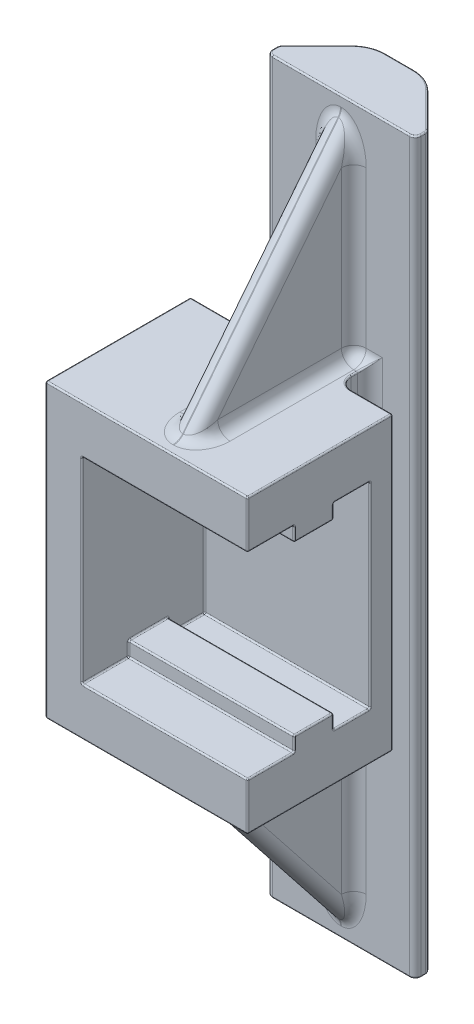
SolidWorks part; units mm, degrees
ref_plane "Front Plane" through (0, 0, 0) normal (0, 0, 1) x (1, 0, 0)
ref_plane "Top Plane" through (0, 0, 0) normal (0, 1, 0) x (1, 0, 0)
ref_plane "Right Plane" through (0, 0, 0) normal (1, 0, 0) x (0, 0, -1)
sketch "Sketch15" plane through (0, 0, 0) normal (0, 1, 0) x (1, 0, 0)
  line L0 (-3.964, 1.5536) -> (-3.964, 2.5104) construction
  line L1 (-5.6176, 4.164) -> (-9.3853, 4.164)
  line L2 (-10.187, 4.9657) -> (-10.187, 5.534)
  line L3 (-9.9522, 6.1008) -> (-5.2214, 10.8317)
  line L4 (-1.9335, 12.1936) -> (1.9335, 12.1936)
  line L5 (5.2214, 10.8317) -> (9.9522, 6.1008)
  line L6 (10.187, 5.534) -> (10.187, 4.9657)
  line L7 (9.3853, 4.164) -> (5.6176, 4.164)
  line L8 (3.964, 2.5104) -> (3.964, 1.5536) construction
  line L9 (-5.6176, 4.164) -> (5.6176, 4.164)
  line L130 (-14.3277, 0) -> (-9.4961, 0) construction
  line L131 (-7.9763, 0) -> (-5.6176, 0) construction
  line L132 (-4.064, 1.5536) -> (-4.064, 2.5104) construction
  line L133 (-5.6176, 4.064) -> (-9.3853, 4.064) construction
  line L134 (-10.287, 4.9657) -> (-10.287, 5.534) construction
  line L135 (-10.0229, 6.1716) -> (-5.2921, 10.9024) construction
  line L136 (-1.9335, 12.2936) -> (1.9335, 12.2936) construction
  line L137 (5.2921, 10.9024) -> (10.0229, 6.1716) construction
  line L138 (10.287, 5.534) -> (10.287, 4.9657) construction
  line L139 (9.3853, 4.064) -> (5.6176, 4.064) construction
  line L140 (4.064, 2.5104) -> (4.064, 1.5536) construction
  line L141 (5.6176, 0) -> (7.9763, 0) construction
  line L142 (9.4961, 0) -> (14.3277, 0) construction
  arc A0 (-5.6176, -0.1) -> (-3.964, 1.5536) centre (-5.6176, 1.5536) ccw construction
  arc A1 (-3.964, 2.5104) -> (-5.6176, 4.164) centre (-5.6176, 2.5104) ccw construction
  arc A2 (-10.187, 4.9657) -> (-9.3853, 4.164) centre (-9.3853, 4.9657) ccw
  arc A3 (-9.9522, 6.1008) -> (-10.187, 5.534) centre (-9.3853, 5.534) ccw
  arc A4 (-1.9335, 12.1936) -> (-5.2214, 10.8317) centre (-1.9335, 7.5438) ccw
  arc A5 (5.2214, 10.8317) -> (1.9335, 12.1936) centre (1.9335, 7.5438) ccw
  arc A6 (10.187, 5.534) -> (9.9522, 6.1008) centre (9.3853, 5.534) ccw
  arc A7 (9.3853, 4.164) -> (10.187, 4.9657) centre (9.3853, 4.9657) ccw
  arc A8 (5.6176, 4.164) -> (3.964, 2.5104) centre (5.6176, 2.5104) ccw construction
  arc A9 (3.964, 1.5536) -> (5.6176, -0.1) centre (5.6176, 1.5536) ccw construction
  arc A151 (-19.05, 3.2025) -> (-15.8475, 0) centre (-15.8751, 3.1749) ccw construction
  arc A152 (-14.3277, 0) -> (-15.8475, 0) centre (-15.0876, 0.0567) ccw construction
  arc A153 (-7.9763, 0) -> (-9.4961, 0) centre (-8.7362, 0.0567) ccw construction
  arc A154 (-5.6176, 0) -> (-4.064, 1.5536) centre (-5.6176, 1.5536) ccw construction
  arc A155 (-4.064, 2.5104) -> (-5.6176, 4.064) centre (-5.6176, 2.5104) ccw construction
  arc A156 (-10.287, 4.9657) -> (-9.3853, 4.064) centre (-9.3853, 4.9657) ccw construction
  arc A157 (-10.0229, 6.1716) -> (-10.287, 5.534) centre (-9.3853, 5.534) ccw construction
  arc A158 (-1.9335, 12.2936) -> (-5.2921, 10.9024) centre (-1.9335, 7.5438) ccw construction
  arc A159 (5.2921, 10.9024) -> (1.9335, 12.2936) centre (1.9335, 7.5438) ccw construction
  arc A160 (10.287, 5.534) -> (10.0229, 6.1716) centre (9.3853, 5.534) ccw construction
  arc A161 (9.3853, 4.064) -> (10.287, 4.9657) centre (9.3853, 4.9657) ccw construction
  arc A162 (5.6176, 4.064) -> (4.064, 2.5104) centre (5.6176, 2.5104) ccw construction
  arc A163 (4.064, 1.5536) -> (5.6176, 0) centre (5.6176, 1.5536) ccw construction
  arc A164 (9.4961, 0) -> (7.9763, 0) centre (8.7362, 0.0567) ccw construction
  point P0 (11.9119, 0)
  dimension "D1" = 0.1
extrude "Boss-Extrude6" add sketch "Sketch15" along normal mid plane 100
sketch "Sketch1" plane through (0, 0, 0) normal (0, 1, 0) x (1, 0, 0)
  line L5 (11.35, -0.1) -> (11.35, -20)
  line L6 (5.6176, -0.1) -> (8.093, -0.1) construction
  line L7 (-16.35, -20) -> (11.35, -20)
  line L8 (-5.6176, -0.1) -> (-3.964, -0.1)
  line L9 (-3.964, -0.1) -> (-3.964, 1.5536)
  line L10 (-3.964, 2.5104) -> (-3.964, 5)
  line L11 (3.964, 1.5536) -> (3.964, -0.1)
  line L12 (3.964, 2.5104) -> (3.964, 5)
  line L13 (3.964, -0.1) -> (5.6176, -0.1)
  line L14 (-14.3277, 0) -> (-9.4961, 0) construction
  line L15 (-14.4445, -0.1) -> (-16.35, -0.1)
  line L16 (5.6176, 0) -> (7.9763, 0) construction
  line L17 (4.064, 2.5104) -> (4.064, 1.5536) construction
  line L18 (9.3853, 4.064) -> (5.6176, 4.064) construction
  line L19 (-7.9763, 0) -> (-5.6176, 0) construction
  line L20 (-4.064, 1.5536) -> (-4.064, 2.5104) construction
  line L21 (-5.6176, 4.064) -> (-9.3853, 4.064) construction
  line L22 (-14.4445, -0.1) -> (-9.3794, -0.1)
  line L23 (-8.093, -0.1) -> (-5.6176, -0.1)
  line L24 (-3.964, 1.5536) -> (-3.964, 2.5104)
  line L26 (-16.35, -0.1) -> (-16.35, -20)
  line L27 (3.964, 2.5104) -> (3.964, 1.5536)
  line L28 (5.6176, -0.1) -> (11.35, -0.1)
  line L30 (9.3853, 4.164) -> (5.6176, 4.164) construction
  line L31 (-5.6176, 4.164) -> (-9.3853, 4.164) construction
  line L32 (3.964, 5) -> (-3.964, 5)
  line L35 (9.3794, -0.1) -> (14.4445, -0.1) construction
  line L36 (9.4961, 0) -> (14.3277, 0) construction
  arc A0 (-8.093, -0.1) -> (-9.3794, -0.1) centre (-8.7362, -0.1) ccw
  arc A10 (-19.05, 3.2025) -> (-15.8475, 0) centre (-15.8751, 3.1749) ccw construction
  arc A11 (-14.3277, 0) -> (-15.8475, 0) centre (-15.0876, 0.0567) ccw construction
  arc A12 (-7.9763, 0) -> (-9.4961, 0) centre (-8.7362, 0.0567) ccw construction
  arc A15 (9.4961, 0) -> (7.9763, 0) centre (8.7362, 0.0567) ccw construction
  arc A16 (4.064, 1.5536) -> (5.6176, 0) centre (5.6176, 1.5536) ccw construction
  arc A17 (5.6176, 4.064) -> (4.064, 2.5104) centre (5.6176, 2.5104) ccw construction
  arc A18 (-5.6176, 0) -> (-4.064, 1.5536) centre (-5.6176, 1.5536) ccw construction
  arc A19 (-4.064, 2.5104) -> (-5.6176, 4.064) centre (-5.6176, 2.5104) ccw construction
  arc A23 (-5.6176, -0.1) -> (-3.964, 1.5536) centre (-5.6176, 1.5536) ccw construction
  arc A24 (-3.964, 2.5104) -> (-5.6176, 4.164) centre (-5.6176, 2.5104) ccw construction
  arc A25 (5.6176, 4.164) -> (3.964, 2.5104) centre (5.6176, 2.5104) ccw construction
  arc A26 (3.964, 1.5536) -> (5.6176, -0.1) centre (5.6176, 1.5536) ccw construction
  arc A30 (15.7315, -0.097) -> (14.4445, -0.1) centre (15.0876, 0.0567) ccw construction
  arc A31 (15.7315, -0.097) -> (19.15, 3.2034) centre (15.8751, 3.1749) ccw construction
  arc A32 (15.8475, 0) -> (19.05, 3.2025) centre (15.8751, 3.1749) ccw construction
  arc A33 (15.8475, 0) -> (14.3277, 0) centre (15.0876, 0.0567) ccw construction
  arc A34 (-19.15, 3.2034) -> (-15.7315, -0.097) centre (-15.8751, 3.1749) ccw construction
  arc A35 (-14.4445, -0.1) -> (-15.7315, -0.097) centre (-15.0876, 0.0567) ccw construction
  arc A36 (-8.093, -0.1) -> (-9.3794, -0.1) centre (-8.7362, 0.0567) ccw construction
  arc A37 (9.3794, -0.1) -> (8.093, -0.1) centre (8.7362, 0.0567) ccw construction
  point P0 (0, 0)
  dimension "D1" = 5
  dimension "D2" = 20
  dimension "D4" = 11.35
  dimension "D5" = 16.35
  dimension "D3" = 0.1
extrude "Boss-Extrude1" add sketch "Sketch1" along normal mid plane 40
sketch "Sketch12" plane through (11.35, 0, 0) normal (1, 0, 0) x (0, 0, -1)
  line L0 (-22.6, 13.45) -> (-22.6, -13.45)
  line L2 (-22.6, 13.45) -> (-13.6, 13.45)
  line L3 (-13.6, 13.45) -> (-13.6, 11.45)
  line L4 (-13.6, 11.45) -> (-8.2, 11.45)
  line L5 (-8.2, 11.45) -> (-8.2, 13.45)
  line L6 (-8.2, 13.45) -> (-3.2, 13.45)
  line L7 (-3.2, 13.45) -> (-3.2, -13.45)
  line L8 (-3.2, -13.45) -> (-8.2, -13.45)
  line L9 (-8.2, -13.45) -> (-8.2, -11.45)
  line L10 (-8.2, -11.45) -> (-13.6, -11.45)
  line L11 (-13.6, -11.45) -> (-13.6, -13.45)
  line L12 (-13.6, -13.45) -> (-22.6, -13.45)
  line L13 (-0.1, 0) -> (-22.6, 0) construction
  line L14 (-0.1, 20) -> (-0.1, -20) construction
  point P5 (-22.6, 0)
  dimension "D1" = 26.9
  dimension "D2" = 9
  dimension "D3" = 5.4
  dimension "D4" = 5
  dimension "D5" = 2
  dimension "D6" = 3.2
extrude "Cut-Extrude4" cut sketch "Sketch12" against normal blind 22.7
sketch "Sketch16" plane through (0, 0, 0) normal (1, 0, 0) x (0, 0, -1)
  line L0 (4.164, 50) -> (4.164, -50) construction
  line L1 (-0.1, 20) -> (4.164, 20) construction
  line L2 (-20, 20) -> (-0.1, 20) construction
  line L3 (4.164, 50) -> (4.164, -50) construction
  line L4 (-0.1, 20) -> (4.164, 20) construction
  line L5 (-20, 20) -> (-0.1, 20) construction
  line L6 (-18, 20) -> (4.164, 48)
  dimension "D1" = 2
  dimension "D2" = 2
rib "Rib1" sketch "Sketch16" sketch "Sketch16" thickness 3.5 extrusion direction parallel to sketch draft on no parameters "D1"=3.5
mirror "Mirror1" about plane through (0, 0, 0) normal (0, 1, 0) of "Rib1"
fillet "Fillet1" radius 1.7 24 edges at (0, -20, 18) (0, -48, -4.164) (-1.75, 20, 6.918) (1.75, -34, 6.918) (1.75, -20, 6.918) (1.75, -34, -4.164) (-1.75, -34, 6.918) (-1.75, -34, -4.164) (-1.75, -20, 6.918) (2.857, -20, -4.164) (-2.857, -20, -4.164) (-1.75, 34, 6.918) (1.75, 34, 6.918) (0, 20, 18) (1.75, 34, -4.164) (1.75, 20, 6.918) (2.857, 20, -4.164) (3.964, 0, -4.164) (3.964, 0, 0.1) (-3.964, 0, 0.1) (0, 48, -4.164) (-1.75, 34, -4.164) (-2.857, 20, -4.164) (-3.964, 0, -4.164)
fillet "Fillet2" radius 0.2 91 edges at (-8.7362, 20, -0.5432) (-8.7362, -20, -0.5432) (8.507, 20, 0.1) (4.4619, 20, -0.3979) (3.964, 20, -2.032) (4.4619, -20.4979, -3.6661) (3.964, -20, -2.032) (8.507, -20, 0.1) (-4.4619, 20.4979, -3.6661) (-3.964, 20, -2.032) (-6.8785, 20, 0.1) (-4.4619, -20.4979, -3.6661) (-3.964, -20, -2.032) (-4.4619, -20, -0.3979) (-7.5868, -50, -8.4663) (-10.126, -50, -5.8408) (-10.187, -50, -5.2498) (-9.9522, -50, -4.3988) (0, -50, -4.164) (9.9522, -50, -4.3988) (10.187, -50, -5.2498) (10.126, -50, -5.8408) (7.5868, -50, -8.4663) (3.7129, -50, -11.8397) (0, -50, -12.1936) (-3.7129, -50, -11.8397) (3.7129, 50, -11.8397) (7.5868, 50, -8.4663) (10.126, 50, -5.8408) (10.187, 50, -5.2498) (9.9522, 50, -4.3988) (0, 50, -4.164) (-9.9522, 50, -4.3988) (-10.187, 50, -5.2498) (-10.126, 50, -5.8408) (-7.5868, 50, -8.4663) (-3.7129, 50, -11.8397) (0, 50, -12.1936) (-9.3794, 0, 0.1) (-12.8647, 20, 0.1) (-12.8647, -20, 0.1) (-2.5, -20, 20) (-2.5, 20, 20) (11.35, -12.45, 8.2) (11.35, 13.45, 5.7) (11.35, 12.45, 8.2) (11.35, 16.725, 20) (11.35, 20, 10.05) (11.35, 0, 0.1) (11.35, -20, 10.05) (11.35, -16.725, 20) (11.35, -12.45, 13.6) (0, -13.45, 20) (0, -13.45, 13.6) (11.35, -13.45, 16.8) (0, -11.45, 13.6) (0, -11.45, 8.2) (11.35, -11.45, 10.9) (0, -13.45, 8.2) (11.35, -13.45, 5.7) (0, -13.45, 3.2) (0, 13.45, 3.2) (11.35, 0, 3.2) (0, 11.45, 8.2) (11.35, 11.45, 10.9) (0, 11.45, 13.6) (11.35, 12.45, 13.6) (0, 13.45, 13.6) (0, 13.45, 20) (11.35, 13.45, 16.8) (-11.35, 0, 20) (-11.35, 13.45, 16.8) (-11.35, 12.45, 13.6) (-11.35, 11.45, 10.9) (-11.35, 12.45, 8.2) (-11.35, 13.45, 5.7) (-11.35, 0, 3.2) (-11.35, -13.45, 5.7) (-11.35, -12.45, 8.2) (-11.35, -11.45, 10.9) (-11.35, -12.45, 13.6) (-11.35, -13.45, 16.8) (4.4619, 20.4979, -3.6661) (4.4619, -20, -0.3979) (-4.4619, 20, -0.3979) (-6.8785, -20, 0.1) (0, 13.45, 8.2) (-16.35, 0, 0.1) (-16.35, 0, 20) (-16.35, 20, 10.05) (-16.35, -20, 10.05)
equation "\"D5@Sketch1\"=\"D4@Sketch1\"+5"
